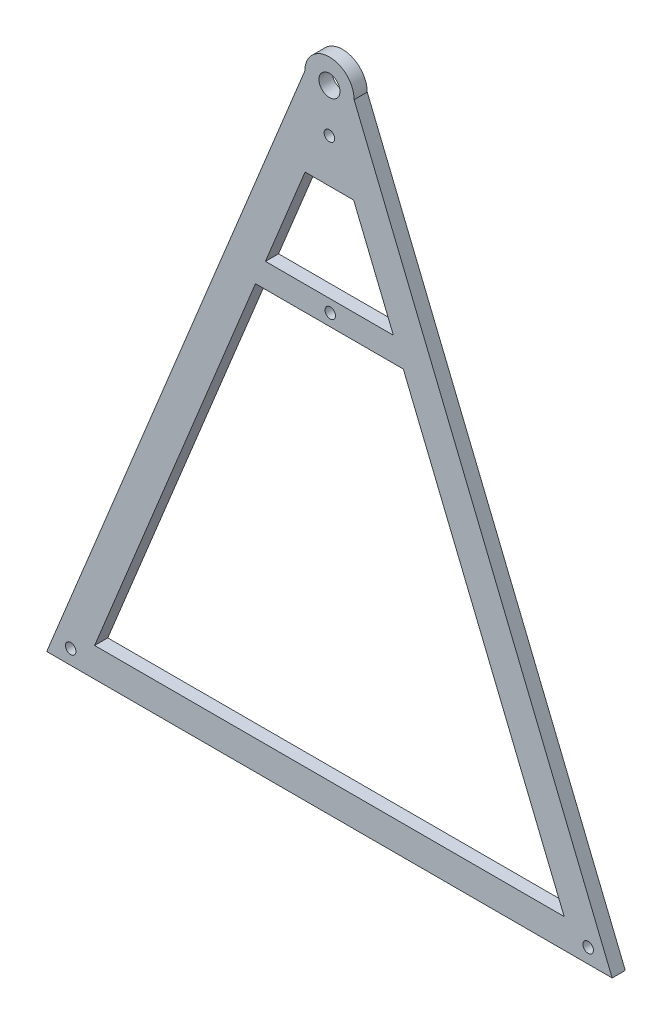
SolidWorks part; units mm, degrees
ref_plane "Front Plane" through (0, 0, 0) normal (0, 0, 1) x (1, 0, 0)
ref_plane "Top Plane" through (0, 0, 0) normal (0, 1, 0) x (1, 0, 0)
ref_plane "Right Plane" through (0, 0, 0) normal (1, 0, 0) x (0, 0, -1)
sketch "Sketch1" plane through (0, 0, 0) normal (0, 0, 1) x (1, 0, 0)
  line L0 (-11.9419, 0) -> (-136.7702, -305.5545)
  line L1 (0, 0) -> (11.9419, 0) construction
  line L2 (0, 0) -> (-11.9419, 0) construction
  line L3 (11.9419, 0) -> (136.7702, -305.5545)
  line L4 (-136.7702, -305.5545) -> (136.7702, -305.5545)
  line L5 (11.729, -42.1747) -> (-11.7704, -42.1747)
  line L6 (113.5524, -291.4179) -> (-113.5937, -291.4179)
  line L7 (113.5524, -291.4179) -> (11.729, -42.1747)
  line L8 (-11.7704, -42.1747) -> (-113.5937, -291.4179)
  circle A0 centre (0, 0) radius 5.08
  circle A1 centre (0, 0) radius 11.9419
extrude "Boss-Extrude2" add sketch "Sketch1" along normal blind 6.35 contours A1 L0 L4 L3 L8 L5 L7 L6 | A1 A0 region at (0, -16.043, 0) region at (0, 11.6042, 0)
sketch "Sketch2" plane through (0, 0, 6.35) normal (0, 0, 1) x (1, 0, 0)
  line L0 (113.5524, -291.4179) -> (136.7702, -305.5545) construction
  line L1 (-113.5937, -291.4179) -> (-136.7702, -305.5545) construction
  circle A0 centre (125.1613, -298.4862) radius 2.54
extrude "Cut-Extrude1" cut sketch "Sketch2" against normal blind 6.35
sketch "Sketch3" plane through (0, 0, 6.35) normal (0, 0, 1) x (1, 0, 0)
  line L0 (-113.5937, -291.4179) -> (-136.7702, -305.5545) construction
  line L1 (-136.7702, -305.5545) -> (136.7702, -305.5545) construction
  line L2 (-11.9419, 0) -> (-136.7702, -305.5545) construction
  circle A0 centre (-125.182, -298.4862) radius 2.54
extrude "Cut-Extrude2" cut sketch "Sketch3" against normal blind 6.35
sketch "Sketch4" plane through (0, 0, 6.35) normal (0, 0, 1) x (1, 0, 0)
  line L0 (0, 0) -> (-0.0207, -42.1747) construction
  line L1 (11.729, -42.1747) -> (-11.7704, -42.1747) construction
  circle A0 centre (-0.0103, -21.0873) radius 2.54
extrude "Cut-Extrude3" cut sketch "Sketch4" against normal blind 6.35
sketch "Sketch5" plane through (0, 0, 6.35) normal (0, 0, 1) x (1, 0, 0)
  line L0 (-30.9786, -89.1927) -> (30.9373, -89.1927)
  line L1 (-11.7704, -42.1747) -> (-113.5937, -291.4179) construction
  line L2 (113.5524, -291.4179) -> (11.729, -42.1747) construction
  line L3 (-35.7816, -100.9494) -> (35.7403, -100.9494)
  line L6 (30.9373, -89.1927) -> (35.7403, -100.9494)
  line L7 (-30.9786, -89.1927) -> (-35.7816, -100.9494)
extrude "Boss-Extrude4" add sketch "Sketch5" against normal blind 6.35
sketch "Sketch6" plane through (0, 0, 6.35) normal (0, 0, 1) x (1, 0, 0)
  line L0 (-31.1877, -95.1115) -> (32.005, -95.1115) construction
  line L1 (-0.0103, -21.0873) -> (0.4087, -95.1115) construction
  circle A0 centre (0.4087, -95.1115) radius 2.54
extrude "Cut-Extrude4" cut sketch "Sketch6" against normal blind 6.35
